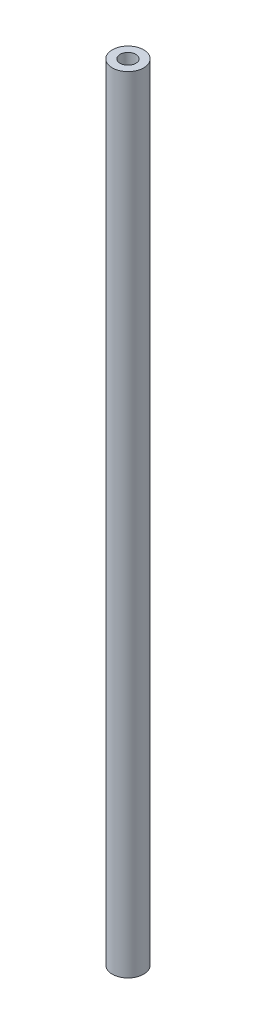
SolidWorks part; units mm, degrees
ref_plane "前视基准面" through (0, 0, 0) normal (0, 0, 1) x (1, 0, 0)
ref_plane "上视基准面" through (0, 0, 0) normal (0, 1, 0) x (1, 0, 0)
ref_plane "右视基准面" through (0, 0, 0) normal (1, 0, 0) x (0, 0, -1)
sketch "草图1" plane through (0, 0, 0) normal (0, 1, 0) x (1, 0, 0)
  circle A0 centre (0, 0) radius 4
  dimension "D1" = 8
extrude "凸台-拉伸1" add sketch "草图1" along normal blind 200
sketch "草图2" plane through (0, 200, 0) normal (0, 1, 0) x (1, 0, 0)
  circle A0 centre (0, 0) radius 2
  dimension "D1" = 4
extrude "切除-拉伸1" cut sketch "草图2" against normal through all
